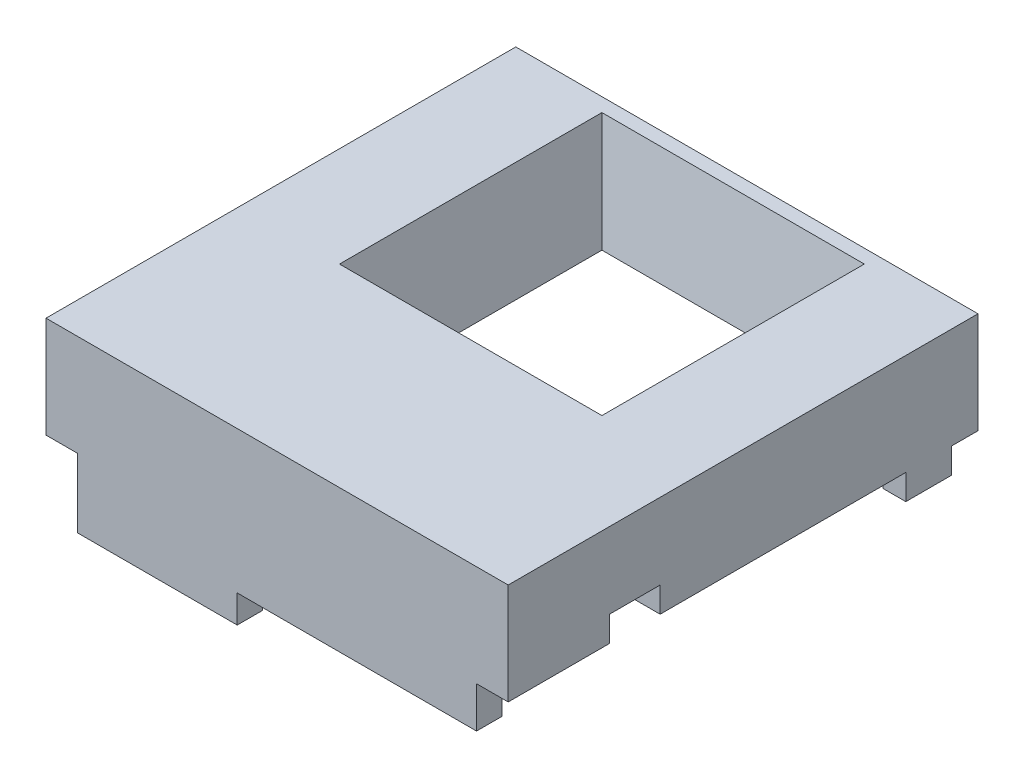
SolidWorks part; units mm, degrees
ref_plane "Front Plane" through (0, 0, 0) normal (0, 0, 1) x (1, 0, 0)
ref_plane "Top Plane" through (0, 0, 0) normal (0, 1, 0) x (1, 0, 0)
ref_plane "Right Plane" through (0, 0, 0) normal (1, 0, 0) x (0, 0, -1)
sketch "Sketch1" plane through (0, 0, 0) normal (0, 1, 0) x (1, 0, 0)
  line L1 (0, 0) -> (36.5, 0)
  line L2 (0, 0) -> (0, -37.1)
  line L3 (0, -37.1) -> (36.5, -37.1)
  line L4 (36.5, 0) -> (36.5, -37.1)
  dimension "D1" = 37.1
  dimension "D2" = 36.5
extrude "Body" add sketch "Sketch1" along normal blind 8
sketch "Sketch2" plane through (0, 0, 0) normal (0, -1, 0) x (-1, 0, 0)
  line L0 (-36.5, 0) -> (0, 0) construction
  line L1 (0, -6.1) -> (-2, -6.1)
  line L2 (0, -6.1) -> (0, -2.1)
  line L3 (0, -2.1) -> (-2, -2.1)
  line L4 (-2, -6.1) -> (-2, -2.1)
  line L5 (-34.5, -29.1) -> (-36.5, -29.1)
  line L6 (-34.5, -29.1) -> (-34.5, -25.1)
  line L7 (-34.5, -25.1) -> (-36.5, -25.1)
  line L8 (-36.5, -29.1) -> (-36.5, -25.1)
  line L10 (0, 0) -> (0, -37.1) construction
  line L11 (0, -37.1) -> (-36.5, -37.1) construction
  line L13 (-36.5, -37.1) -> (-36.5, 0) construction
  point P10 (-1, -2.1)
  dimension "D1" = 2.1
  dimension "D2" = 4
  dimension "D3" = 2
  dimension "D4" = 8
  dimension "D5" = 4
  dimension "D6" = 2
extrude "Female Tabs" cut sketch "Sketch2" against normal blind 2
sketch "Sketch3" plane through (0, 0, 0) normal (0, -1, 0) x (-1, 0, 0)
  line L0 (-36.5, -29.1) -> (-34.5, -29.1) construction
  line L1 (0, -29.1) -> (-1.8, -29.1)
  line L2 (0, -29.1) -> (0, -25.5)
  line L3 (0, -25.5) -> (-1.8, -25.5)
  line L4 (-1.8, -29.1) -> (-1.8, -25.5)
  line L5 (-34.7, -5.7) -> (-36.5, -5.7)
  line L6 (-34.7, -5.7) -> (-34.7, -2.1)
  line L7 (-34.7, -2.1) -> (-36.5, -2.1)
  line L8 (-36.5, -5.7) -> (-36.5, -2.1)
  line L9 (0, -6.1) -> (0, -37.1) construction
  line L10 (-36.5, -25.1) -> (-36.5, 0) construction
  line L11 (0, -2.1) -> (-2, -2.1) construction
  dimension "D1" = 1.8
  dimension "D2" = 3.6
  dimension "D3" = 1.8
  dimension "D4" = 3.6
extrude "Male Tabs" add sketch "Sketch3" along normal blind 2
sketch "Sketch5" plane through (0, 0, 0) normal (0, -1, 0) x (-1, 0, 0)
  line L0 (-36.5, 0) -> (0, 0) construction
  line L1 (-27.2, -2.5) -> (-9.3, -2.5)
  line L2 (-27.2, -2.5) -> (-27.2, -20.4)
  line L3 (-27.2, -20.4) -> (-9.3, -20.4)
  line L4 (-9.3, -2.5) -> (-9.3, -20.4)
  line L5 (-36.5, -2.1) -> (-36.5, 0) construction
  line L6 (0, -6.1) -> (0, -25.5) construction
  line L7 (0, -37.1) -> (-36.5, -37.1) construction
  dimension "D1" = 2.5
  dimension "D2" = 9.3
  dimension "D3" = 9.3
  dimension "D4" = 16.7
extrude "SiPM Window" cut sketch "Sketch5" against normal up to next (8 mm away) draft 10 draft outward yes
sketch "Sketch6" plane through (0, 0, 0) normal (0, -1, 0) x (1, 0, 0)
  line L0 (36.5, 0) -> (0, 0) construction
  line L1 (34, 1.5) -> (29.2, 1.5)
  line L2 (34, 1.5) -> (34, 35.1)
  line L4 (29.2, 1.5) -> (29.2, 22.4)
  line L5 (29.2, 22.4) -> (7.3, 22.4)
  line L9 (7.3, 1.5) -> (2.5, 1.5)
  line L10 (7.3, 1.5) -> (7.3, 22.4)
  line L13 (36.5, 25.1) -> (36.5, 5.7) construction
  line L16 (34, 35.1) -> (2.5, 35.1)
  line L17 (2.5, 35.1) -> (2.5, 1.5)
  line L18 (0, 6.1) -> (0, 25.5) construction
  line L19 (0, 37.1) -> (36.5, 37.1) construction
  line L20 (27.2, 20.4) -> (9.3, 20.4) construction
  line L21 (9.3, 20.4) -> (9.3, 2.5) construction
  line L22 (27.2, 2.5) -> (27.2, 20.4) construction
  dimension "D1" = 1.5
  dimension "D2" = 1.5
  dimension "D3" = 2.5
  dimension "D4" = 2.5
  dimension "D5" = 2
  dimension "D6" = 2
  dimension "D7" = 2
  dimension "D8" = 2
extrude "Cut-Extrude2" cut sketch "Sketch6" against normal offset from surface (6 mm away) 2 up to face at (18.25, 8, 11.45)
sketch "Sketch7" plane through (0, 0, 0) normal (0, -1, 0) x (1, 0, 0)
  line L0 (0, 37.1) -> (36.5, 37.1) construction
  line L1 (34, 35.1) -> (15.1, 35.1)
  line L2 (34, 35.1) -> (34, 37.1)
  line L3 (34, 37.1) -> (15.1, 37.1)
  line L4 (15.1, 35.1) -> (15.1, 37.1)
  line L5 (0, 29.1) -> (0, 37.1) construction
  dimension "D1" = 15.1
extrude "Right Drop" add sketch "Sketch7" along normal blind 3.24
sketch "Sketch8" plane through (0, 0, 0) normal (0, -1, 0) x (1, 0, 0)
  line L1 (15.1, 37.1) -> (2.5, 37.1)
  line L2 (15.1, 37.1) -> (15.1, 35.1)
  line L3 (15.1, 35.1) -> (2.5, 35.1)
  line L4 (2.5, 37.1) -> (2.5, 35.1)
extrude "Left Drop" add sketch "Sketch8" along normal blind 5.44
